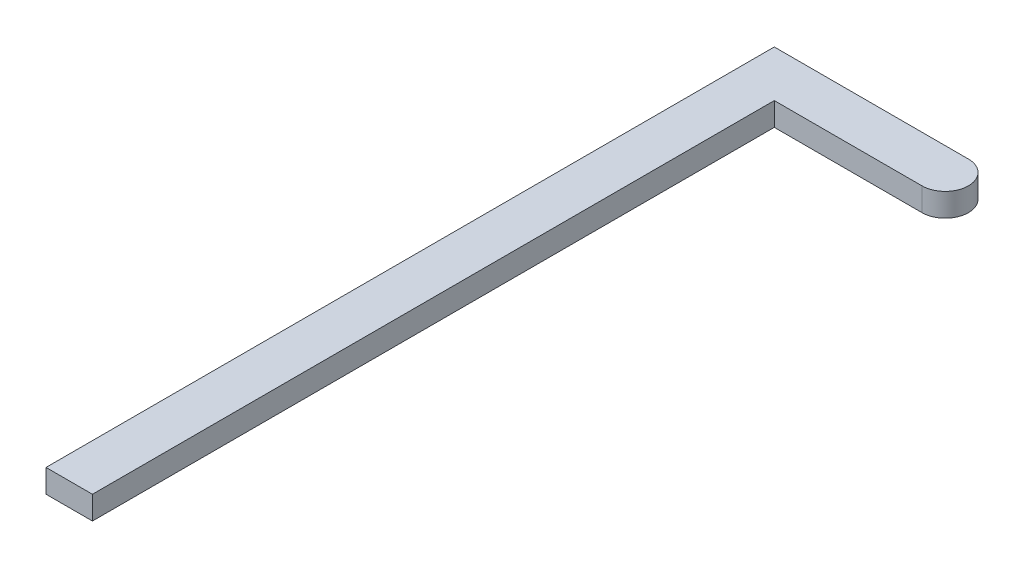
SolidWorks part; units mm, degrees
ref_plane "Front Plane" through (0, 0, 0) normal (0, 0, 1) x (1, 0, 0)
ref_plane "Top Plane" through (0, 0, 0) normal (0, 1, 0) x (1, 0, 0)
ref_plane "Right Plane" through (0, 0, 0) normal (1, 0, 0) x (0, 0, -1)
sketch "Sketch1" plane through (0, 0, 0) normal (0, 1, 0) x (1, 0, 0)
  line L0 (0, 0) -> (-46.736, 0) construction
  line L1 (-46.736, 0) -> (-46.736, -192.786) construction
  line L2 (0, 6.35) -> (-53.086, 6.35)
  line L3 (-53.086, 6.35) -> (-53.086, -192.786)
  line L4 (0, -6.35) -> (-40.386, -6.35)
  line L5 (-40.386, -6.35) -> (-40.386, -192.786)
  line L6 (-53.086, -192.786) -> (-40.386, -192.786)
  arc A0 (0, 6.35) -> (0, -6.35) centre (0, 0) cw
  dimension "D1" = 192.786
  dimension "D2" = 53.086
  dimension "D3" = 6.35
  dimension "D4" = 6.35
extrude "Boss-Extrude1" add sketch "Sketch1" along normal blind 6.35
